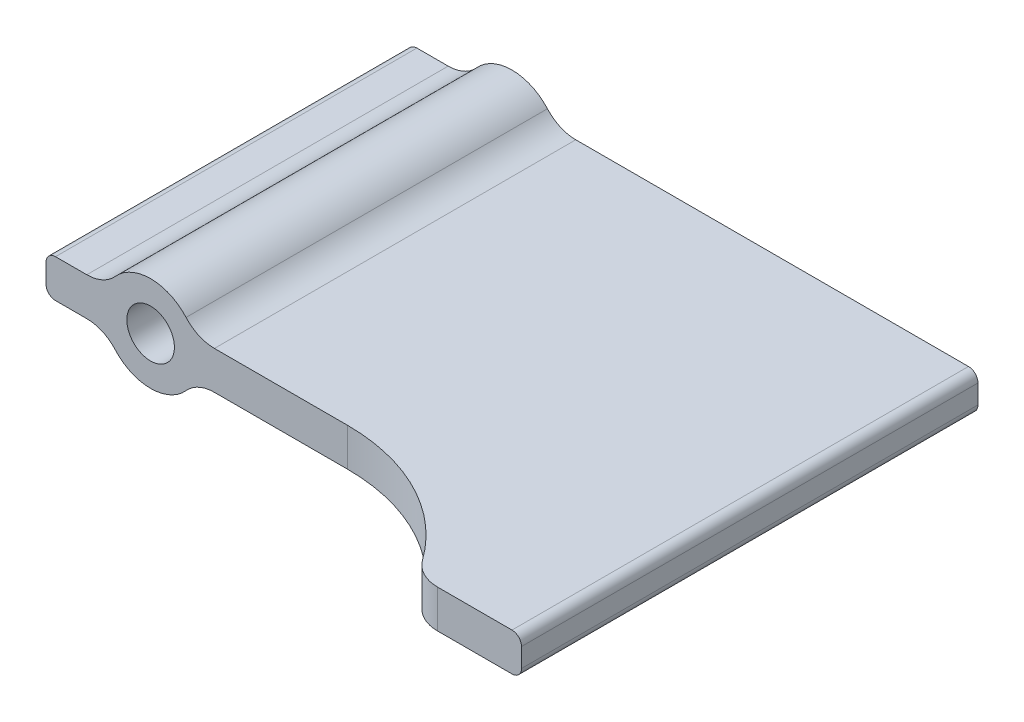
SolidWorks part; units mm, degrees
ref_plane "Front Plane" through (0, 0, 0) normal (0, 0, 1) x (1, 0, 0)
ref_plane "Top Plane" through (0, 0, 0) normal (0, 1, 0) x (1, 0, 0)
ref_plane "Right Plane" through (0, 0, 0) normal (1, 0, 0) x (0, 0, -1)
sketch "Sketch1" plane through (0, 0, 0) normal (0, 0, 1) x (1, 0, 0)
  line L0 (-943.663, 304.3873) -> (-956.6481, 304.3873) construction
  line L1 (-943.663, 304.3873) -> (-916.4663, 304.3873) construction
  line L3 (-948.663, 303.3873) -> (-947.0171, 303.3873)
  line L4 (-949.163, 303.8873) -> (-949.163, 304.8873)
  line L5 (-948.663, 305.3873) -> (-947.0171, 305.3873)
  line L6 (-919.163, 303.8873) -> (-919.163, 304.8873)
  line L7 (-949.163, 303.3873) -> (-919.163, 305.3873) construction
  line L8 (-949.163, 305.3873) -> (-919.163, 303.3873) construction
  line L9 (-940.3089, 305.3873) -> (-919.663, 305.3873)
  line L10 (-940.3089, 303.3873) -> (-919.663, 303.3873)
  arc A0 (-945.5264, 302.7207) -> (-941.7996, 302.7207) centre (-943.663, 304.3873) ccw
  arc A1 (-941.7996, 306.054) -> (-945.5264, 306.054) centre (-943.663, 304.3873) ccw
  arc A2 (-945.5264, 302.7207) -> (-947.0171, 303.3873) centre (-947.0171, 301.3873) ccw
  arc A3 (-941.7996, 302.7207) -> (-940.3089, 303.3873) centre (-940.3089, 301.3873) cw
  arc A4 (-941.7996, 306.054) -> (-940.3089, 305.3873) centre (-940.3089, 307.3873) ccw
  arc A5 (-947.0171, 305.3873) -> (-945.5264, 306.054) centre (-947.0171, 307.3873) ccw
  arc A6 (-948.663, 303.3873) -> (-949.163, 303.8873) centre (-948.663, 303.8873) cw
  circle A7 centre (-943.663, 304.3873) radius 1.25
  arc A8 (-949.163, 304.8873) -> (-948.663, 305.3873) centre (-948.663, 304.8873) cw
  arc A9 (-919.663, 303.3873) -> (-919.163, 303.8873) centre (-919.663, 303.8873) ccw
  arc A10 (-919.663, 305.3873) -> (-919.163, 304.8873) centre (-919.663, 304.8873) cw
  point P3 (-934.163, 304.3873)
  point P19 (-941.3717, 303.3873)
  point P22 (-941.3717, 305.3873)
  dimension "D4" = 5
  dimension "D5" = 2
  dimension "D6" = 0.5
  dimension "D7" = 0.5
  dimension "D8" = 2.5
  dimension "D1" = 2
  dimension "D2" = 5.5
  dimension "D3" = 30
extrude "Boss-Extrude1" add sketch "Sketch1" along normal blind 9.5 and the other way blind 9.5
sketch "Sketch2" plane through (0, 0, 9.5) normal (0, 0, 1) x (1, 0, 0)
  line L0 (-924.663, 305.3873) -> (-924.663, 303.3873)
  line L6 (-948.663, 303.3873) -> (-947.0171, 303.3873)
  line L7 (-940.3089, 303.3873) -> (-919.663, 303.3873)
  line L8 (-919.163, 303.8873) -> (-919.163, 304.8873)
  line L9 (-919.663, 305.3873) -> (-940.3089, 305.3873)
  line L10 (-947.0171, 305.3873) -> (-948.663, 305.3873)
  line L11 (-949.163, 304.8873) -> (-949.163, 303.8873)
  line L13 (-924.663, 303.3873) -> (-919.663, 303.3873)
  line L14 (-919.163, 303.8873) -> (-919.163, 304.8873)
  line L15 (-919.663, 305.3873) -> (-924.663, 305.3873)
  arc A10 (-949.163, 303.8873) -> (-948.663, 303.3873) centre (-948.663, 303.8873) ccw
  arc A11 (-945.5264, 302.7207) -> (-947.0171, 303.3873) centre (-947.0171, 301.3873) ccw
  arc A12 (-945.5264, 302.7207) -> (-941.7996, 302.7207) centre (-943.663, 304.3873) ccw
  arc A13 (-940.3089, 303.3873) -> (-941.7996, 302.7207) centre (-940.3089, 301.3873) ccw
  arc A14 (-919.663, 303.3873) -> (-919.163, 303.8873) centre (-919.663, 303.8873) ccw
  arc A15 (-919.163, 304.8873) -> (-919.663, 305.3873) centre (-919.663, 304.8873) ccw
  arc A16 (-941.7996, 306.054) -> (-940.3089, 305.3873) centre (-940.3089, 307.3873) ccw
  arc A17 (-941.7996, 306.054) -> (-945.5264, 306.054) centre (-943.663, 304.3873) ccw
  arc A18 (-947.0171, 305.3873) -> (-945.5264, 306.054) centre (-947.0171, 307.3873) ccw
  arc A19 (-948.663, 305.3873) -> (-949.163, 304.8873) centre (-948.663, 304.8873) ccw
  arc A24 (-919.663, 303.3873) -> (-919.163, 303.8873) centre (-919.663, 303.8873) ccw
  arc A25 (-919.163, 304.8873) -> (-919.663, 305.3873) centre (-919.663, 304.8873) ccw
  dimension "D2" = 5
  dimension "D1" = 0
extrude "Boss-Extrude2" add sketch "Sketch2" along normal blind 5
fillet "Fillet1" radius 10 1 edges at (-924.663, 304.3873, 9.5)
fillet "Fillet2" radius 2 1 edges at (-924.663, 304.3873, 14.5)
